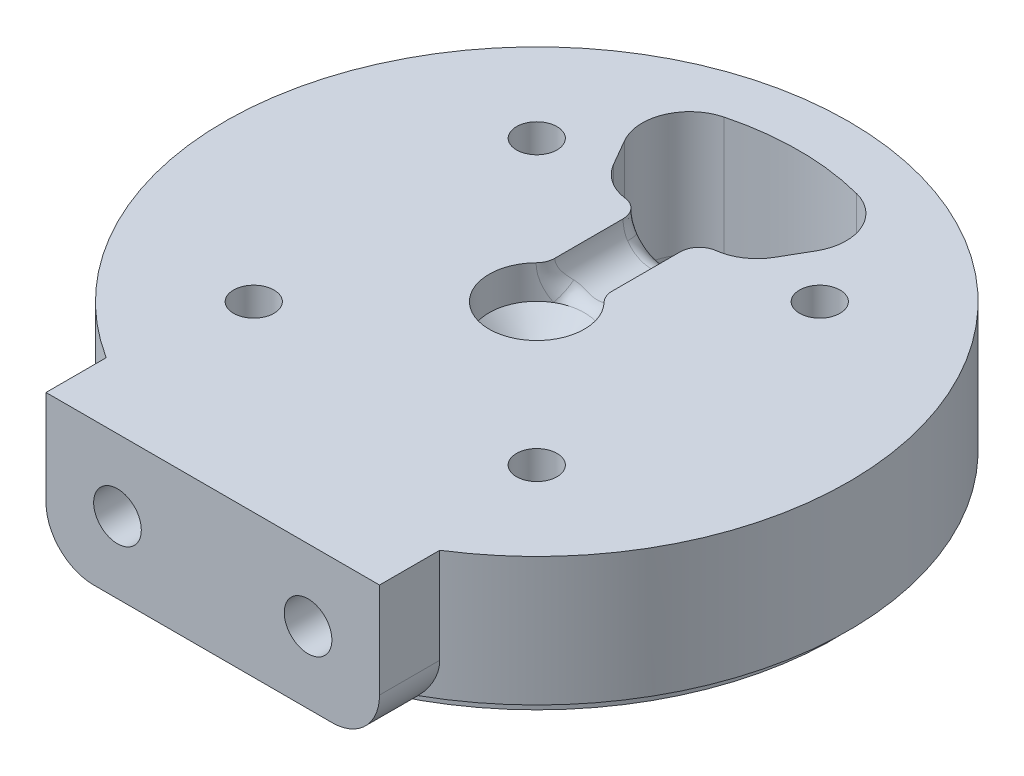
SolidWorks part; units mm, degrees
ref_plane "Front Plane" through (0, 0, 0) normal (0, 0, 1) x (1, 0, 0)
ref_plane "Top Plane" through (0, 0, 0) normal (0, 1, 0) x (1, 0, 0)
ref_plane "Right Plane" through (0, 0, 0) normal (1, 0, 0) x (0, 0, -1)
sketch "Sketch1" plane through (0, 0, 0) normal (0, 1, 0) x (1, 0, 0)
  circle A2 centre (0, 0) radius 32.75
  dimension "D1" = 65.5
extrude "Boss-Extrude1" add sketch "Sketch1" along normal mid plane 15
sketch "Sketch2" plane through (0, 7.5, 0) normal (0, 1, 0) x (1, 0, 0)
  circle A0 centre (0, 0) radius 2.5
  dimension "D1" = 5
extrude "Cut-Extrude1" cut sketch "Sketch2" against normal through all
sketch "Sketch3" plane through (0, 7.5, 0) normal (0, 1, 0) x (1, 0, 0)
  line L0 (-544.3881, -544.3881) -> (26675.0155, 26675.0155) construction
  line L1 (0, -1000) -> (0, 49000) construction
  circle A0 centre (14.8492, 14.8492) radius 2.125
  dimension "D1" = 4.25
  dimension "D2" = 21
  dimension "D3" = 45
extrude "Cut-Extrude2" cut sketch "Sketch3" against normal through all
sketch "Sketch14" plane through (0, -7.5, 0) normal (0, -1, 0) x (1, 0, 0)
  circle A0 centre (14.8492, -14.8492) radius 3.375
  dimension "D1" = 6.75
extrude "Cut-Extrude10" cut sketch "Sketch14" against normal offset from surface (5 mm away) 10 up to face at (14.8492, 7.5, -12.7242)
pattern_circular "CirPattern1" count 4 over 360 about axis through (0, 7.5, 0) along (0, 1, 0) of "Cut-Extrude2", "Cut-Extrude10"
sketch "Sketch4" plane through (0, 7.5, 0) normal (0, 1, 0) x (1, 0, 0)
  line L0 (0, 14) -> (7, 14)
  line L1 (7, 14) -> (12.9298, 24.2708)
  line L4 (0, 27.5) -> (0, -48146.9727) construction
  line L5 (0, 27.5) -> (0, 14)
  arc A0 (12.9298, 24.2708) -> (0, 27.5) centre (0, 0) ccw
  dimension "D2" = 55
  dimension "D1" = 14
  dimension "D3" = 120
  dimension "D6" = 7
extrude "Cut-Extrude3" cut sketch "Sketch4" against normal through all
mirror "Mirror1" about plane through (0, -7.5, -27.5) normal (-1, 0, 0) of "Cut-Extrude3"
sketch "Sketch7" plane through (0, 7.5, 0) normal (0, 1, 0) x (1, 0, 0)
  circle A0 centre (0, 0) radius 5
  dimension "D1" = 10
extrude "Cut-Extrude6" cut sketch "Sketch7" against normal blind 7.5
chamfer "Chamfer1" distance 4 angle 45 1 edges at (0, 0, 5)
sketch "Sketch11" plane through (0, 0, 0) normal (0, 0, 1) x (1, 0, 0)
  line L0 (32.75, 7.5) -> (-32.75, 7.5) construction
  line L1 (-12.5, -7.5) -> (12.5, -7.5)
  line L2 (-17.5, -2.5) -> (-17.5, 7.5)
  line L3 (-17.5, 7.5) -> (17.5, 7.5)
  line L4 (17.5, -2.5) -> (17.5, 7.5)
  line L5 (-17.5, -7.5) -> (17.5, 7.5) construction
  line L6 (-17.5, 7.5) -> (17.5, -7.5) construction
  arc A2 (17.5, -2.5) -> (12.5, -7.5) centre (12.5, -2.5) cw
  arc A3 (-12.5, -7.5) -> (-17.5, -2.5) centre (-12.5, -2.5) cw
  point P0 (0, 0)
  dimension "D2" = 5
  dimension "D1" = 35
extrude "Boss-Extrude2" add sketch "Sketch11" along normal blind 7 from offset 27
sketch "Sketch9" plane through (0, 0, 34) normal (0, 0, 1) x (1, 0, 0)
  line L1 (-12.5, -7.5) -> (12.5, -7.5) construction
  line L10 (0, -1000) -> (0, 49000) construction
  line L12 (-10, 0) -> (10, 0) construction
  circle A3 centre (10, 0) radius 2.5
  circle A4 centre (-10, 0) radius 2.5
  point P1 (0, 40)
  dimension "D4" = 5
  dimension "D5" = 5
  dimension "D1" = 20
  dimension "D2" = 10
  dimension "D3" = 7.5
extrude "Cut-Extrude7" cut sketch "Sketch9" against normal blind 10
fillet "Fillet1" radius 5 4 edges at (-7, 0, -14) (7, 0, -14) (12.9298, 0, -24.2708) (-12.9298, 0, -24.2708)
sketch "Sketch12" plane through (0, 0, 0) normal (0, 0, 1) x (1, 0, 0)
  line L0 (17.5, 7.5) -> (-17.5, 7.5) construction
  circle A0 centre (0, 7.5) radius 3
  dimension "D1" = 6
extrude "Cut-Extrude8" cut sketch "Sketch12" against normal up to next
sketch "Sketch13" plane through (0, -7.5, 0) normal (0, -1, 0) x (1, 0, 0)
  line L0 (0, 0) -> (-15, 0) construction
  circle A0 centre (-15, 0) radius 1.95
  point P4 (0, 0)
  point P5 (-20.4574, 0)
  dimension "D1" = 3.9
  dimension "D2" = 15
extrude "Cut-Extrude9" cut sketch "Sketch13" against normal blind 10
chamfer "Chamfer2" distance 1 angle 45 1 edges at (-15, -7.5, -1.95)
mirror "Mirror2" about plane through (0, 0, 0) normal (1, 0, 0) of "Cut-Extrude9", "Chamfer2"
fillet "Fillet5" radius 2 6 edges at (-10.3232, -7.5, -23.6893) (-6.6132, -7.5, -14.6699) (0, -7.5, -14) (6.6132, -7.5, -14.6699) (10.3232, -7.5, -23.6893) (0, -7.5, -27.5) tangent propagation no
fillet "Fillet7" radius 2 2 edges at (0, 4.5, -14) (0.1077, 4.5019, -4.9988)
sketch "Sketch15" plane through (0, -7.5, 0) normal (0, -1, 0) x (1, 0, 0)
  circle A0 centre (0, 0) radius 31.25
  circle A1 centre (0, 0) radius 32.75
  arc A2 (-12.5, 30.2707) -> (12.5, 30.2707) centre (0, 0) ccw construction
  dimension "D1" = 1.5
extrude "Cut-Extrude11" cut sketch "Sketch15" against normal blind 1.5
sketch "Sketch16" plane through (0, -6, 0) normal (0, -1, 0) x (1, 0, 0)
  line L0 (0, -1000) -> (0, 49000) construction
  line L1 (0.75, 33.6368) -> (-0.75, 33.6368)
  line L2 (0.75, 33.6368) -> (0.75, 30.3202)
  line L3 (0.75, 30.3202) -> (-0.75, 30.3202)
  line L4 (-0.75, 33.6368) -> (-0.75, 30.3202)
  line L5 (0.75, 33.6368) -> (-0.75, 30.3202) construction
  line L6 (0.75, 30.3202) -> (-0.75, 33.6368) construction
  point P0 (0, 31.9785)
  point P6 (0, 0)
  dimension "D1" = 1.5
extrude "Boss-Extrude3" add sketch "Sketch16" along normal up to surface (1.5 mm away) up to face at (0, -7.5, 32.7552)
